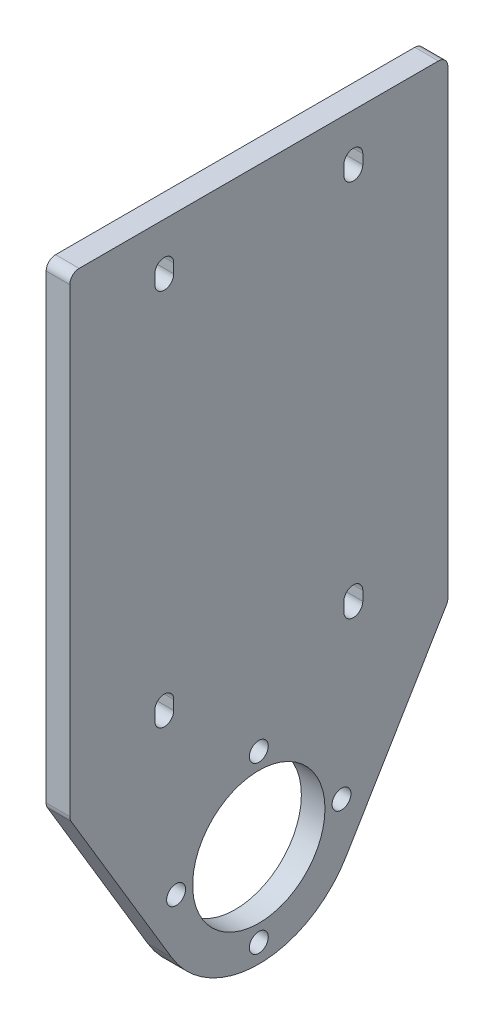
SolidWorks part; units mm, degrees
ref_plane "Front Plane" through (0, 0, 0) normal (0, 0, 1) x (1, 0, 0)
ref_plane "Top Plane" through (0, 0, 0) normal (0, 1, 0) x (1, 0, 0)
ref_plane "Right Plane" through (0, 0, 0) normal (1, 0, 0) x (0, 0, -1)
sketch "Sketch1" plane through (0, 0, 0) normal (1, 0, 0) x (0, 0, -1)
  line L0 (0, 0) -> (0, -75) construction
  line L1 (-40, 50) -> (40, 50)
  line L2 (-40, 50) -> (-40, -50)
  line L3 (-40, -50) -> (40, -50)
  line L4 (40, 50) -> (40, -50)
  line L5 (-40, 50) -> (40, -50) construction
  line L6 (-40, -50) -> (40, 50) construction
  line L7 (0, 0) -> (40, 0) construction
  line L8 (-40, 40) -> (40, 40) construction
  line L9 (-20, 41) -> (-20, 39) construction
  line L10 (-18, 41) -> (-18, 39)
  line L11 (-22, 41) -> (-22, 39)
  line L12 (20, 41) -> (20, 39) construction
  line L13 (18, 41) -> (18, 39)
  line L14 (22, 41) -> (22, 39)
  line L15 (-20, -41) -> (-20, -39) construction
  line L16 (-18, -41) -> (-18, -39)
  line L17 (-22, -41) -> (-22, -39)
  line L18 (20, -41) -> (20, -39) construction
  line L19 (18, -41) -> (18, -39)
  line L20 (22, -41) -> (22, -39)
  line L21 (-40, -50) -> (-18.4526, -86.0341)
  line L22 (40, -50) -> (18.4526, -86.0341)
  arc A0 (-18, 41) -> (-22, 41) centre (-20, 41) ccw
  arc A1 (-22, 39) -> (-18, 39) centre (-20, 39) ccw
  arc A2 (18, 41) -> (22, 41) centre (20, 41) cw
  arc A3 (22, 39) -> (18, 39) centre (20, 39) cw
  arc A4 (-18, -41) -> (-22, -41) centre (-20, -41) cw
  arc A5 (-22, -39) -> (-18, -39) centre (-20, -39) cw
  arc A6 (18, -41) -> (22, -41) centre (20, -41) ccw
  arc A7 (22, -39) -> (18, -39) centre (20, -39) ccw
  circle A8 centre (0, -75) radius 14
  circle A9 centre (0, -75) radius 17.5 construction
  circle A10 centre (17.5, -75) radius 2
  circle A11 centre (0, -92.5) radius 2
  circle A12 centre (-17.5, -75) radius 2
  circle A13 centre (0, -57.5) radius 2
  circle A14 centre (0, -75) radius 21.5
  point P0 (0, 0)
  point P14 (-20, 40)
  point P22 (20, 40)
  point P27 (-20, -40)
  point P34 (20, -40)
  point P51 (0, -75)
  dimension "D2" = 2
  dimension "D6" = 28
  dimension "D7" = 35
  dimension "D8" = 4
  dimension "D10" = 43
  dimension "D11" = 25
  dimension "D1" = 100
  dimension "D3" = 2
  dimension "D4" = 10
  dimension "D5" = 20
  dimension "D12" = 80
  dimension "D9" = 4
extrude "Boss-Extrude1" add sketch "Sketch1" along normal blind 5 contours L4 L1 L2 L3 A7 L20 A6 L19 A1 L11 A0 L10 L14 A3 L13 A2 L17 A5 L16 A4 | A14 L22 L3 L21 | A14 A8 A10 A11 A12 A13 region at (0, 0, 0) region at (0, -50.8774, 0) region at (0, -54.862, 5.5617)
fillet "Fillet1" radius 2 4 edges at (2.5, -50, -40) (2.5, -50, 40) (2.5, 50, -40) (2.5, 50, 40)
